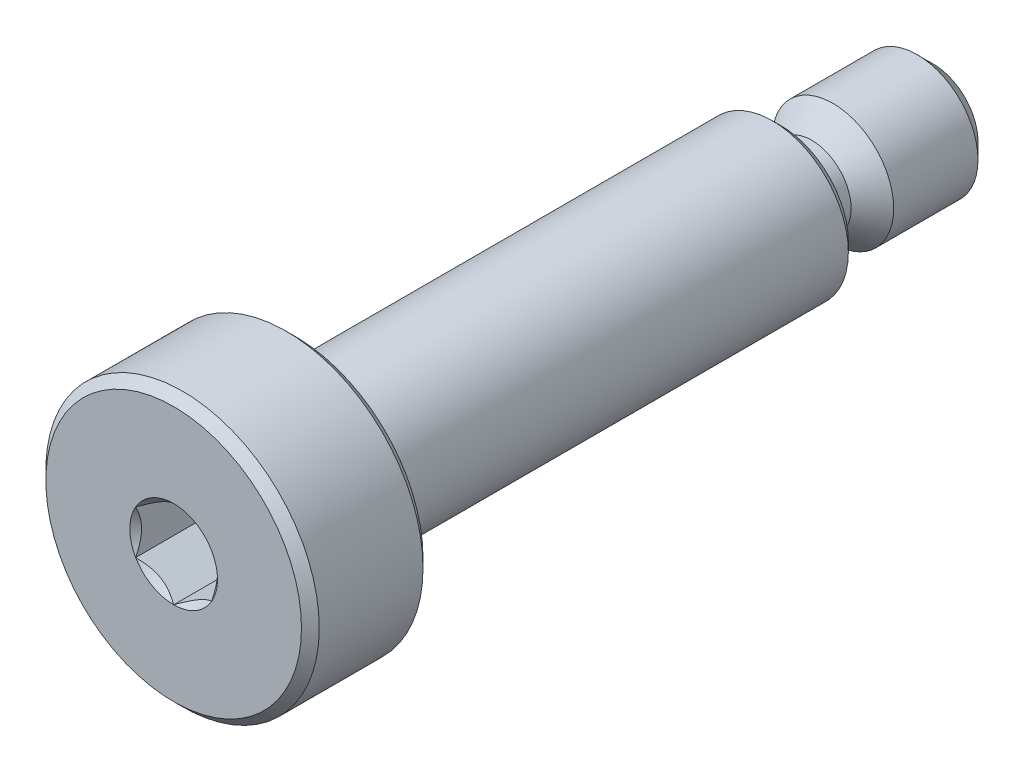
SolidWorks part; units mm, degrees
ref_plane "Front Plane" through (0, 0, 0) normal (0, 0, 1) x (1, 0, 0)
ref_plane "Top Plane" through (0, 0, 0) normal (0, 1, 0) x (1, 0, 0)
ref_plane "Right Plane" through (0, 0, 0) normal (1, 0, 0) x (0, 0, -1)
sketch "Sketch1" plane through (0, 0, 0) normal (1, 0, 0) x (0, 0, -1)
  line L0 (-12.5, 0) -> (12.5, 0) construction
  line L1 (-12.5, -4.5) -> (-12.5, 4.5) construction
  line L2 (-12.5, 4.5) -> (-8.5, 4.5) construction
  line L3 (-8.5, 4.5) -> (-8.5, 2.297) construction
  line L4 (-8.5, 2.297) -> (-7.992, 2.297) construction
  line L5 (-7.992, 2.297) -> (-7.789, 2.5) construction
  line L6 (-7.789, 2.5) -> (7.5, 2.5) construction
  line L7 (12.4562, 2.0758) -> (12.8062, 1.4696) construction
  line L8 (12.8062, 1.4696) -> (13.1562, 2.0758) construction
  line L9 (12.5, -2) -> (12.5, 2) construction
  line L10 (7.5, 2.5) -> (12.5, 2.5) construction
  line L11 (13.1562, 2.0758) -> (12.4562, 2.0758) construction
  line L12 (12.8062, 2.0758) -> (12.8062, 2) construction
  line L13 (12.8062, 1.4696) -> (12.8062, 1.5453) construction
  line L14 (12.85, 1.5453) -> (12.7625, 1.5453) construction
  line L15 (13.1125, 2) -> (12.5, 2) construction
  line L16 (12.8062, 2.0379) -> (13.1344, 2.0379) construction
  line L17 (12.8062, 2.0379) -> (12.4781, 2.0379) construction
  line L18 (-12.5, 4.2075) -> (-12.2075, 4.5) construction
  line L19 (-8.7925, 4.5) -> (-8.5, 4.2075) construction
  line L20 (12.5, 2) -> (7.5, 2) construction
  line L21 (11.975, 2) -> (12.5, 1.475) construction
  line L22 (9.2, 2) -> (8.5, 1.3) construction
  line L23 (8.5, 1.3) -> (7.85, 1.3) construction
  line L24 (7.5, 2) -> (7.5, 1.65) construction
  line L25 (-10.5, 1.25) -> (-10.5, -1.25) construction
  line L26 (-10.5, -1.25) -> (-12.5, -1.25) construction
  line L27 (-10.5, 1.25) -> (-12.5, 1.25) construction
  line L28 (-12.2075, 0) -> (-8.9632, 0) construction
  arc A0 (7.5, 1.65) -> (7.85, 1.3) centre (7.85, 1.65) ccw construction
  point P4 (0, 0)
  point P7 (-12.5, 0)
  point P18 (12.5, 0)
  point P25 (10.05, -2)
  point P38 (-10.5, 4.5)
  point P45 (-10.5, 0)
  point P46 (8.85, 1.65)
  point P48 (-7.992, 0)
  point P51 (-10.5, 0)
  point P52 (7.5, 0)
  dimension "Head Diameter" = 9
  dimension "Head Height" = 4
  dimension "Thread Diameter" = 4
  dimension "Shoulder Diameter" = 5
  dimension "Thread Length" = 5
  dimension "D1" = 0.508
  dimension "D2" = 135
  dimension "D3" = 0.203
  dimension "Shoulder Length" = 16
  dimension "Thread Pitch" = 0.7
  dimension "D4" = 0.0875
  dimension "D5" = 2.45
  dimension "D6" = 0.2925
  dimension "D7" = 0.525
  dimension "D8" = 2.6
  dimension "D9" = 1
  dimension "Drive Size" = 2.5
  dimension "Knurling Length" = 3.2443
sketch "Sketch3" plane through (0, 0, 0) normal (1, 0, 0) x (0, 0, -1)
  line L0 (-12.5, 0) -> (-12.5, 4.2075)
  line L1 (-12.5, -4.5) -> (-12.5, 4.5) construction
  line L2 (-12.5, 4.2075) -> (-12.2075, 4.5)
  line L3 (-12.2075, 4.5) -> (-8.7925, 4.5)
  line L4 (-8.7925, 4.5) -> (-8.5, 4.2075)
  line L5 (-8.5, 4.2075) -> (-8.5, 2.297)
  line L6 (-8.5, 2.297) -> (-7.992, 2.297)
  line L7 (-7.992, 2.297) -> (-7.789, 2.5)
  line L8 (-7.789, 2.5) -> (7.5, 2.5)
  line L9 (7.5, 2.5) -> (7.5, 1.65)
  line L10 (7.85, 1.3) -> (8.5, 1.3)
  line L11 (8.5, 1.3) -> (9.2, 2)
  line L12 (9.2, 2) -> (11.975, 2)
  line L13 (11.975, 2) -> (12.5, 1.475)
  line L14 (12.5, 1.475) -> (12.5, 0)
  line L15 (12.5, 0) -> (-12.5, 0)
  arc A0 (7.5, 1.65) -> (7.85, 1.3) centre (7.85, 1.65) ccw construction
  arc A1 (7.5, 1.65) -> (7.85, 1.3) centre (7.85, 1.65) ccw
revolve "Revolve1" add sketch "Sketch3" angle 360 about L0
sketch "Sketch4" plane through (0, 0, 0) normal (0, 0, 1) x (1, 0, 0)
  line L0 (0, -4.5) -> (0, 4.5) construction
  line L1 (0, 1.4434) -> (-1.25, 0.7217)
  line L2 (-1.25, 0.7217) -> (-1.25, -0.7217)
  line L3 (-1.25, -0.7217) -> (0, -1.4434)
  line L4 (0, -1.4434) -> (1.25, -0.7217)
  line L5 (1.25, -0.7217) -> (1.25, 0.7217)
  line L6 (1.25, 0.7217) -> (0, 1.4434)
  circle A0 centre (0, 0) radius 1.25 construction
extrude "Cut-Extrude1" cut sketch "Sketch4" against normal up to vertex (-10.5 mm away) from vertex up to point (0, 0, 10.5) starting at point (0, 0, 12.5)
sketch "Sketch5" plane through (0, 0, 0) normal (0, 0, 1) x (1, 0, 0)
  line L0 (0, -4.5) -> (0, 4.5) construction
  circle A0 centre (0, 0) radius 1.4434
extrude "Cut-Extrude2" cut sketch "Sketch5" against normal up to vertex (-10.5 mm away) draft 45 from vertex up to point (0, 0, 10.5) starting at point (0, 0, 12.5)
chamfer "Chamfer1" distance 0.2925 angle 45 1 edges at (2.5, 0, -7.5)
sketch "Sketch6" [suppressed] plane through (0, 0, -12.5) normal (0, 0, -1) x (-1, 0, 0)
  circle A0 centre (0, 0) radius 2
curve "Helix/Spiral1" [suppressed] pitch 0.7 height 4.75 turns 6.7857
sketch "Sketch7" [suppressed] plane through (0, 0, 0) normal (1, 0, 0) x (0, 0, -1)
  line L0 (12.4781, 2.0379) -> (12.7625, 1.5453)
  line L1 (12.7625, 1.5453) -> (12.85, 1.5453)
  line L2 (12.85, 1.5453) -> (13.1344, 2.0379)
  line L3 (13.1344, 2.0379) -> (12.4781, 2.0379)
sweep "Cut-Sweep1" [suppressed] cut profiles "Sketch7" path "Helix/Spiral1"
sketch "Sketch8" [suppressed] plane through (0, 0, 0) normal (0, 0, 1) x (1, 0, 0)
  line L0 (0, 4.5) -> (0, 0) construction
  line L1 (-0.1351, 4.5) -> (0.1351, 4.5)
  line L2 (0.1351, 4.5) -> (0, 4.266)
  line L3 (0, 4.266) -> (-0.1351, 4.5)
  line L4 (-0.1351, 4.5) -> (0, 0) construction
  line L5 (0, 0) -> (0.1351, 4.5) construction
  circle A0 centre (0, 0) radius 4.266 construction
  point P8 (0, 4.5)
  dimension "D1" = 0.234
  dimension "D2" = 3.439
extrude "Cut-Extrude3" [suppressed] cut sketch "Sketch8" against normal up to vertex from vertex
pattern_circular "CirPattern1" [suppressed] count 99 over 360 about axis through (0, 0, 12.5) along (0, 0, -1) of bodies 108
equation "\"D4@Sketch1\"=\"Thread Pitch@Sketch1\"/8"
equation "\"D5@Sketch1\"=\"Thread Pitch@Sketch1\"*3.5"
equation "\"D6@Sketch1\"=\"Head Diameter@Sketch1\"*.0325"
equation "\"D7@Sketch1\"=\"Thread Pitch@Sketch1\"*.75"
equation "\"D8@Sketch1\"=\"Thread Diameter@Sketch1\"*.65"
equation "\"D9@Sketch1\"=\"Thread Length@Sketch1\"*.2"
equation "\"D1@Chamfer1\"=\"D6@Sketch1\""
equation "\"D4@Helix/Spiral1\"=\"Thread Pitch@Sketch1\""
equation "\"D3@Helix/Spiral1\"=\"Thread Length@Sketch1\"*.95"
equation "\"D1@Sketch8\"=\"D6@Sketch1\"*.8"
equation "\"D1@CirPattern1\"=(360/\"D2@Sketch8\")-6"
equation "\"D1@Cut-Extrude3\"=\"D11@Sketch1\""
